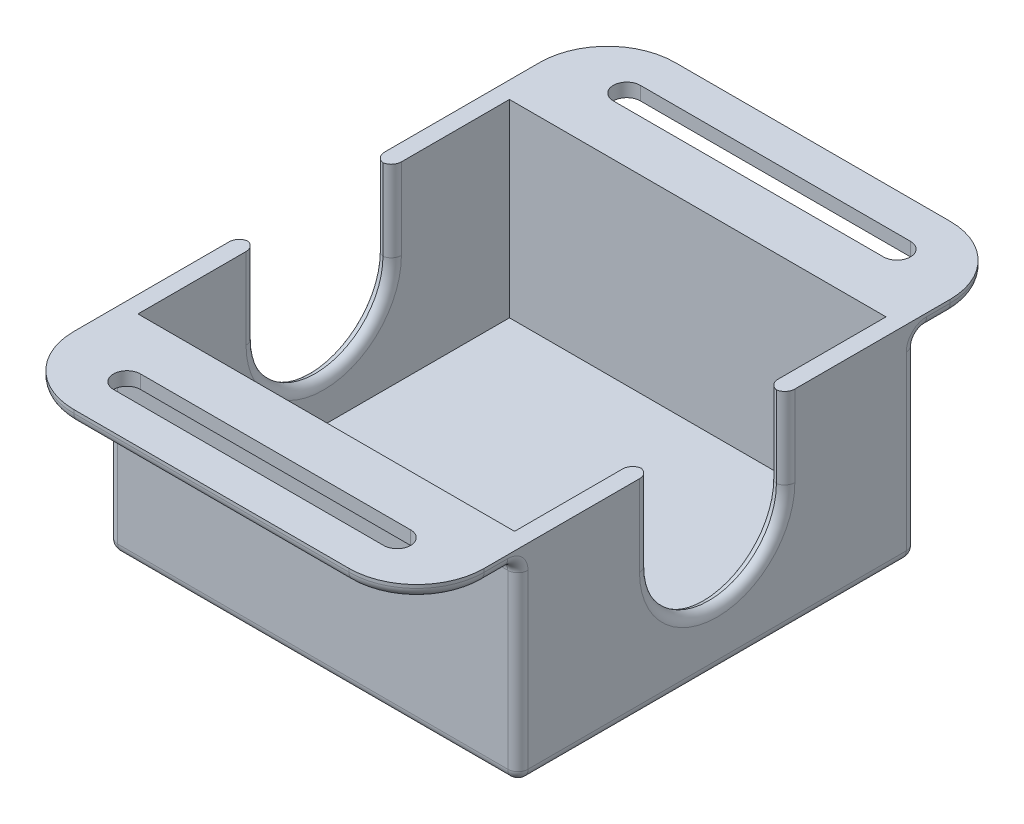
SolidWorks part; units mm, degrees
ref_plane "Front Plane" through (0, 0, 0) normal (0, 0, 1) x (1, 0, 0)
ref_plane "Top Plane" through (0, 0, 0) normal (0, 1, 0) x (1, 0, 0)
ref_plane "Right Plane" through (0, 0, 0) normal (1, 0, 0) x (0, 0, -1)
sketch "Sketch2" plane through (0, 0, 0) normal (0, 0, 1) x (1, 0, 0)
  line L0 (-23.875, -1.5) -> (-27.875, -1.5)
  line L1 (-27.875, -1.5) -> (-27.875, -27)
  line L2 (-27.875, -27) -> (0, -27)
  line L3 (0, 0) -> (0, -54) construction
  line L4 (-23.875, 1) -> (-30.375, 1)
  line L5 (-30.375, 1) -> (-30.375, -29.5)
  line L6 (-30.375, -29.5) -> (0, -29.5)
  line L7 (-23.875, 1) -> (-23.875, -1.5)
  line L8 (23.875, 1) -> (23.875, -1.5)
  line L9 (30.375, -29.5) -> (0, -29.5)
  line L10 (30.375, 1) -> (30.375, -29.5)
  line L11 (23.875, 1) -> (30.375, 1)
  line L12 (27.875, -27) -> (0, -27)
  line L13 (27.875, -1.5) -> (27.875, -27)
  line L14 (23.875, -1.5) -> (27.875, -1.5)
  dimension "D1" = 25.5
  dimension "D2" = 27.875
  dimension "D3" = 4
  dimension "D5" = 27
  dimension "D4" = 2.5
extrude "Boss-Extrude1" add sketch "Sketch2" along normal blind 27.5 and the other way blind 27.5
sketch "Sketch3" plane through (0, 0, -27.5) normal (0, 0, -1) x (-1, 0, 0)
  line L1 (-30.375, 1) -> (30.375, 1)
  line L2 (-30.375, 1) -> (-30.375, -29.5)
  line L3 (-30.375, -29.5) -> (30.375, -29.5)
  line L4 (30.375, 1) -> (30.375, -29.5)
extrude "Boss-Extrude2" add sketch "Sketch3" along normal blind 2
sketch "Sketch4" plane through (0, -27, 0) normal (0, 1, 0) x (1, 0, 0)
  line L4 (-27.875, 27.5) -> (-27.875, -27.5)
  line L5 (-27.875, -27.5) -> (27.875, -27.5)
  line L6 (27.875, -27.5) -> (27.875, 27.5)
  line L7 (27.875, 27.5) -> (-27.875, 27.5)
  line L8 (-27.875, 27.5) -> (-27.875, -27.5)
  line L9 (-27.875, -27.5) -> (27.875, -27.5)
  line L10 (27.875, -27.5) -> (27.875, 27.5)
  line L11 (27.875, 27.5) -> (-27.875, 27.5)
  dimension "D1" = 0
extrude "Cut-Extrude1" cut sketch "Sketch4" along normal blind 50
sketch "Sketch5" plane through (0, 0, 27.5) normal (0, 0, 1) x (1, 0, 0)
  line L1 (-30.375, 1) -> (30.375, 1)
  line L2 (-30.375, 1) -> (-30.375, -29.5)
  line L3 (-30.375, -29.5) -> (30.375, -29.5)
  line L4 (30.375, 1) -> (30.375, -29.5)
extrude "Boss-Extrude3" add sketch "Sketch5" along normal blind 2
sketch "Sketch7" plane through (0, -27, 0) normal (0, 1, 0) x (1, 0, 0)
  line L0 (27.875, 27.5) -> (-27.875, 27.5) construction
  line L1 (-2.75, 22) -> (2.75, 22)
  line L2 (-2.75, 22) -> (-2.75, 18)
  line L3 (-2.75, 18) -> (2.75, 18)
  line L4 (2.75, 22) -> (2.75, 18)
  line L5 (-2.75, 22) -> (2.75, 18) construction
  line L6 (-2.75, 18) -> (2.75, 22) construction
  line L7 (14.75, 22) -> (20.25, 22)
  line L8 (14.75, 22) -> (14.75, 18)
  line L9 (14.75, 18) -> (20.25, 18)
  line L10 (20.25, 22) -> (20.25, 18)
  line L11 (14.75, 22) -> (20.25, 18) construction
  line L12 (14.75, 18) -> (20.25, 22) construction
  line L13 (-20.25, 22) -> (-14.75, 22)
  line L14 (-20.25, 22) -> (-20.25, 18)
  line L15 (-20.25, 18) -> (-14.75, 18)
  line L16 (-14.75, 22) -> (-14.75, 18)
  line L17 (-20.25, 22) -> (-14.75, 18) construction
  line L18 (-20.25, 18) -> (-14.75, 22) construction
  point P0 (0, 20)
  point P5 (17.5, 20)
  point P10 (-17.5, 20)
  point P15 (0, 0)
  point P19 (20.25, 23.1076)
  dimension "D1" = 5.5
  dimension "D2" = 4
  dimension "D3" = 12
  dimension "D4" = 12
  dimension "D5" = 5.5
extrude "Cut-Extrude2" cut sketch "Sketch7" against normal blind 2
sketch "Sketch8" plane through (0, 1, 0) normal (0, 1, 0) x (1, 0, 0)
  line L0 (30.375, 29.5) -> (30.375, -29.5) construction
  line L1 (-30.375, 29.5) -> (30.375, 29.5)
  line L2 (-30.375, 29.5) -> (-30.375, 44.5)
  line L3 (-30.375, 44.5) -> (30.375, 44.5)
  line L4 (30.375, 29.5) -> (30.375, 44.5)
  line L5 (-30.375, -29.5) -> (30.375, -29.5)
  line L6 (-30.375, -29.5) -> (-30.375, -44.5)
  line L7 (-30.375, -44.5) -> (30.375, -44.5)
  line L8 (30.375, -29.5) -> (30.375, -44.5)
  line L9 (-20, 37) -> (20, 37) construction
  line L10 (-20, 39) -> (20, 39)
  line L11 (-20, 35) -> (20, 35)
  line L12 (-20, -37) -> (20, -37) construction
  line L13 (-20, -35) -> (20, -35)
  line L14 (-20, -39) -> (20, -39)
  arc A0 (-20, 39) -> (-20, 35) centre (-20, 37) ccw
  arc A1 (20, 35) -> (20, 39) centre (20, 37) ccw
  arc A2 (-20, -35) -> (-20, -39) centre (-20, -37) ccw
  arc A3 (20, -39) -> (20, -35) centre (20, -37) ccw
  point P14 (0, 37)
  point P20 (0, -37)
  point P26 (0, 0)
  point P27 (-30.375, 37)
  point P29 (-30.375, -37)
  dimension "D1" = 15
  dimension "D2" = 40
  dimension "D3" = 4
extrude "Boss-Extrude5" add sketch "Sketch8" against normal blind 2
fillet "Fillet2" radius 10 4 edges at (30.375, 0, -44.5) (-30.375, 0, -44.5) (30.375, 0, 44.5) (-30.375, 0, 44.5)
sketch "Sketch9" plane through (0, 0, 0) normal (1, 0, 0) x (0, 0, -1)
  line L0 (0, 13) -> (0, -11) construction
  line L1 (34.5, 1) -> (-34.5, 1) construction
  line L2 (10, 13) -> (10, -11)
  line L3 (-10, 13) -> (-10, -11)
  arc A0 (10, 13) -> (-10, 13) centre (0, 13) ccw
  arc A1 (-10, -11) -> (10, -11) centre (0, -11) ccw
  point P5 (0, 1)
  point P10 (0, -4.2752)
  dimension "D1" = 20
  dimension "D2" = 12
extrude "Cut-Extrude3" cut sketch "Sketch9" against normal through all both and the other way through all
sketch "Sketch10" plane through (0, 0, -18) normal (0, 0, -1) x (-1, 0, 0)
  line L24 (-27.875, -27) -> (27.875, -27) construction
  line L25 (-27.875, -27) -> (27.875, -27) construction
  line L27 (20.25, -32.8174) -> (14.75, -32.8174)
  line L28 (20.25, -32.8174) -> (20.25, -27.8)
  line L29 (20.25, -27.8) -> (14.75, -27.8)
  line L30 (14.75, -32.8174) -> (14.75, -27.8)
  line L31 (20.25, -32.8174) -> (14.75, -27.8) construction
  line L32 (20.25, -27.8) -> (14.75, -32.8174) construction
  line L33 (-14.75, -32.8174) -> (-20.25, -32.8174)
  line L34 (-14.75, -32.8174) -> (-14.75, -27.8)
  line L35 (-14.75, -27.8) -> (-20.25, -27.8)
  line L36 (-20.25, -32.8174) -> (-20.25, -27.8)
  line L37 (-14.75, -32.8174) -> (-20.25, -27.8) construction
  line L38 (-14.75, -27.8) -> (-20.25, -32.8174) construction
  point P0 (20.25, -32.8174)
  point P2 (13.7567, -31.6383)
  point P7 (17.5, -30.3087)
  point P17 (-17.5, -30.3087)
  dimension "D1" = 0.8
  dimension "D2" = 29.5
  dimension "D3" = 5.5
  dimension "D4" = 17.5
extrude "Cut-Extrude4" cut sketch "Sketch10" along normal up to surface (4 mm away) up to face at (-17.5, -28, -22)
other "DeleteFace1" face at (0, -29, -20) face at (0, -28, -22) face at (-2.75, -28, -20) face at (2.75, -28, -20) face at (0, -28, -18) and patch yes
sketch "Sketch11" plane through (0, -27, 0) normal (0, 1, 0) x (1, 0, 0)
  line L1 (-23.2128, 6.9072) -> (23.2128, 6.9072)
  line L2 (-23.2128, 6.9072) -> (-23.2128, 24.3451)
  line L3 (-23.2128, 24.3451) -> (23.2128, 24.3451)
  line L4 (23.2128, 6.9072) -> (23.2128, 24.3451)
  line L5 (-23.2128, 6.9072) -> (23.2128, 24.3451) construction
  line L6 (-23.2128, 24.3451) -> (23.2128, 6.9072) construction
  point P0 (0, 15.6262)
extrude "Boss-Extrude6" add sketch "Sketch11" against normal blind 0.8
fillet "Fillet3" radius 1.5 32 edges at (0, -1, 44.5) (-27.4461, -1, 41.5711) (-27.4461, -1, -41.5711) (0, -1, -44.5) (27.4461, -1, 41.5711) (-30.375, -1, 32) (-30.375, -1, -32) (27.4461, -1, -41.5711) (0, -1, 29.5) (30.375, -1, 32) (-30.375, -15.25, 29.5) (-30.375, -15.25, -29.5) (-30.375, -29.5, 0) (0, -1, -29.5) (30.375, -1, -32) (30.375, -15.25, 29.5) (0, -29.5, 29.5) (0, -29.5, -29.5) (30.375, -15.25, -29.5) (30.375, -29.5, 0) (-30.375, -5, 10) (-30.375, -5, -10) (30.375, -5, 10) (30.375, -5, -10) (-30.375, -21, 0) (30.375, -21, 0) (-27.875, -5, 10) (-27.875, -5, -10) (27.875, -5, -10) (27.875, -5, 10) (-27.875, -21, 0) (27.875, -21, 0)
